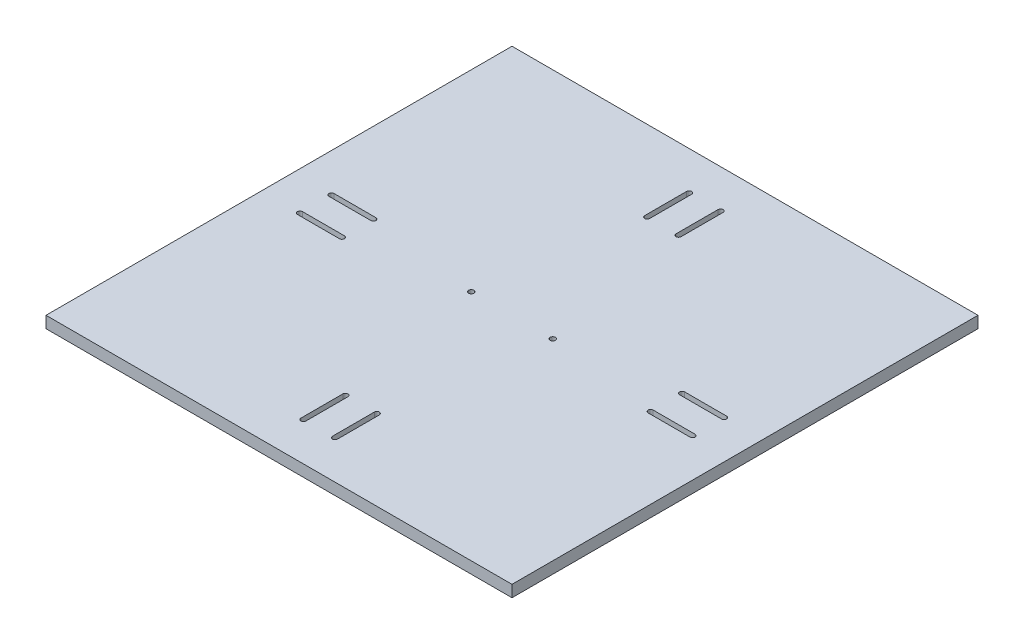
SolidWorks part; units mm, degrees
ref_plane "Plano frontal" through (0, 0, 0) normal (0, 0, 1) x (1, 0, 0)
ref_plane "Plano superior" through (0, 0, 0) normal (0, 1, 0) x (1, 0, 0)
ref_plane "Plano direito" through (0, 0, 0) normal (1, 0, 0) x (0, 0, -1)
sketch "Esboço1" plane through (0, 0, 0) normal (0, 1, 0) x (1, 0, 0)
  line L1 (0, 0) -> (400, 0)
  line L2 (0, 0) -> (0, 400)
  line L3 (0, 400) -> (400, 400)
  line L4 (400, 0) -> (400, 400)
  dimension "D1" = 400
extrude "Ressalto-extrusão1" add sketch "Esboço1" along normal blind 10
sketch "Esboço2" plane through (0, 10, 0) normal (0, 1, 0) x (1, 0, 0)
  line L0 (400, 400) -> (0, 400) construction
  line L1 (182.85, 367) -> (182.85, 331)
  line L2 (187.15, 367) -> (187.15, 331)
  line L3 (209.85, 367) -> (209.85, 331)
  line L4 (214.15, 367) -> (214.15, 331)
  line L5 (0, 200) -> (400, 200) construction
  line L6 (0, 400) -> (0, 0) construction
  line L7 (400, 0) -> (400, 400) construction
  line L8 (200, 400) -> (200, 0) construction
  line L9 (0, 0) -> (400, 0) construction
  line L26 (367, 185.85) -> (331, 185.85)
  line L27 (367, 190.15) -> (331, 190.15)
  line L28 (367, 212.85) -> (331, 212.85)
  line L41 (367, 217.15) -> (331, 217.15)
  line L42 (185.85, 33) -> (185.85, 69)
  line L43 (190.15, 33) -> (190.15, 69)
  line L44 (212.85, 33) -> (212.85, 69)
  line L45 (217.15, 33) -> (217.15, 69)
  line L46 (33, 214.15) -> (69, 214.15)
  line L47 (33, 209.85) -> (69, 209.85)
  line L48 (33, 187.15) -> (69, 187.15)
  line L49 (33, 182.85) -> (69, 182.85)
  arc A0 (187.15, 367) -> (182.85, 367) centre (185, 367) ccw
  arc A1 (182.85, 331) -> (187.15, 331) centre (185, 331) ccw
  arc A2 (214.15, 367) -> (209.85, 367) centre (212, 367) ccw
  arc A3 (209.85, 331) -> (214.15, 331) centre (212, 331) ccw
  arc A32 (367, 185.85) -> (367, 190.15) centre (367, 188) ccw
  arc A33 (331, 190.15) -> (331, 185.85) centre (331, 188) ccw
  arc A34 (331, 217.15) -> (331, 212.85) centre (331, 215) ccw
  arc A35 (367, 212.85) -> (367, 217.15) centre (367, 215) ccw
  arc A36 (185.85, 33) -> (190.15, 33) centre (188, 33) ccw
  arc A37 (190.15, 69) -> (185.85, 69) centre (188, 69) ccw
  arc A38 (217.15, 69) -> (212.85, 69) centre (215, 69) ccw
  arc A39 (212.85, 33) -> (217.15, 33) centre (215, 33) ccw
  arc A40 (33, 214.15) -> (33, 209.85) centre (33, 212) ccw
  arc A41 (69, 209.85) -> (69, 214.15) centre (69, 212) ccw
  arc A42 (69, 182.85) -> (69, 187.15) centre (69, 185) ccw
  arc A43 (33, 187.15) -> (33, 182.85) centre (33, 185) ccw
  point P17 (200, 400)
  point P64 (200, 200)
  dimension "D1" = 4.3
  dimension "D3" = 4.3
  dimension "D2" = 33
  dimension "D4" = 36
  dimension "D5" = 27
  dimension "D6" = 15
  dimension "D7" = 4
sketch "Esboço3" plane through (0, 10, 0) normal (0, 1, 0) x (1, 0, 0)
  line L0 (0, 200) -> (400, 200) construction
  line L1 (0, 400) -> (0, 0) construction
  line L2 (400, 0) -> (400, 400) construction
  line L3 (200, 400) -> (200, 0) construction
  line L4 (400, 400) -> (0, 400) construction
  line L5 (0, 0) -> (400, 0) construction
  circle A0 centre (165, 200) radius 2.25
  circle A1 centre (235, 200) radius 2.25
  dimension "D2" = 4.5
  dimension "D3" = 4.5
  dimension "D1" = 70
  dimension "D4" = 35
extrude "Corte-extrusão3" cut sketch "Esboço3" against normal through all
extrude "Cut-Extrude1" cut sketch "Esboço2" against normal through all
